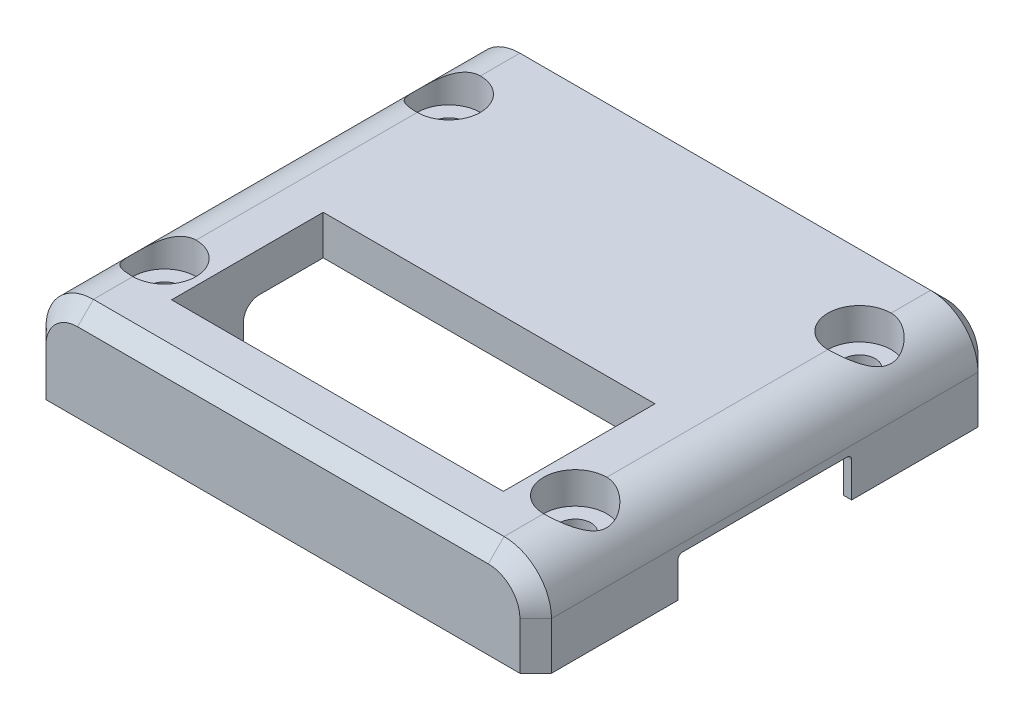
SolidWorks part; units mm, degrees
ref_plane "Front Plane" through (0, 0, 0) normal (0, 0, 1) x (1, 0, 0)
ref_plane "Top Plane" through (0, 0, 0) normal (0, 1, 0) x (1, 0, 0)
ref_plane "Right Plane" through (0, 0, 0) normal (1, 0, 0) x (0, 0, -1)
sketch "Sketch1" plane through (0, 0, 0) normal (0, 1, 0) x (1, 0, 0)
  line L0 (-16, -14.5) -> (16, -14.5)
  line L1 (-16, -14.5) -> (-16, 14.5)
  line L2 (16, -14.5) -> (16, 14.5)
  line L3 (-16, 14.5) -> (16, 14.5)
  line L4 (-16, -14.5) -> (16, 14.5) construction
  line L5 (16, -14.5) -> (-16, 14.5) construction
  point P1 (0, 0)
  dimension "D1" = 32
  dimension "D2" = 29
extrude "Boss-Extrude1" add sketch "Sketch1" along normal blind 6 contours L3 L2 L0 L1
sketch "Sketch2" plane through (0, 6, 0) normal (0, 1, 0) x (1, 0, 0)
  line L0 (-13, -9) -> (13, -9) construction
  line L1 (-13, -9) -> (-13, 9) construction
  line L2 (13, -9) -> (13, 9) construction
  line L3 (-13, 9) -> (13, 9) construction
  line L4 (-13, -9) -> (13, 9) construction
  line L5 (13, -9) -> (-13, 9) construction
  circle A0 centre (-13, 9) radius 1
  circle A1 centre (13, 9) radius 1
  circle A2 centre (13, -9) radius 1
  circle A3 centre (-13, -9) radius 1
  point P1 (0, 0)
  dimension "D1" = 2
  dimension "D2" = 26
  dimension "D3" = 18
extrude "Cut-Extrude1" cut sketch "Sketch2" against normal blind 10
sketch "Sketch3" plane through (0, 6, 0) normal (0, 1, 0) x (1, 0, 0)
  line L0 (0, -6.25) -> (0, 6.25) construction
  line L1 (-10.5, 1.45) -> (10.5, 1.45) construction
  line L2 (-10.5, 1.45) -> (-10.5, 11.05) construction
  line L3 (10.5, 1.45) -> (10.5, 11.05) construction
  line L4 (-10.5, 11.05) -> (10.5, 11.05) construction
  line L5 (-10.5, 1.45) -> (10.5, 11.05) construction
  line L6 (10.5, 1.45) -> (-10.5, 11.05) construction
  line L7 (-10.5, -11.05) -> (10.5, -11.05)
  line L8 (-10.5, -11.05) -> (-10.5, -1.45)
  line L9 (10.5, -11.05) -> (10.5, -1.45)
  line L10 (-10.5, -1.45) -> (10.5, -1.45)
  line L11 (-10.5, -11.05) -> (10.5, -1.45) construction
  line L12 (10.5, -11.05) -> (-10.5, -1.45) construction
  point P4 (0, 0)
  dimension "D1" = 9.6
  dimension "D2" = 21
  dimension "D3" = 12.5
extrude "Cut-Extrude2" cut sketch "Sketch3" against normal blind 10
sketch "Sketch4" plane through (0, 0, 0) normal (0, -1, 0) x (1, 0, 0)
  line L0 (15.5, 13.5) -> (-15.5, 13.5)
  line L1 (15.5, 13.5) -> (15.5, -13.5)
  line L2 (-15.5, 13.5) -> (-15.5, -13.5)
  line L3 (15.5, -13.5) -> (-15.5, -13.5)
  line L4 (15.5, 13.5) -> (-15.5, -13.5) construction
  line L5 (-15.5, 13.5) -> (15.5, -13.5) construction
  line L6 (-16, -14.5) -> (16, -14.5) construction
  point P1 (0, 0)
  dimension "D1" = 31
  dimension "D2" = 1
extrude "Cut-Extrude3" cut sketch "Sketch4" against normal blind 1
fillet "Fillet2" radius 3 2 edges at (-16, 6, 0) (16, 6, 0)
sketch "Sketch5" plane through (0, 6, 0) normal (0, 1, 0) x (1, 0, 0)
  circle A0 centre (-13, 9) radius 2
  circle A1 centre (13, 9) radius 2
  circle A2 centre (13, -9) radius 2
  circle A3 centre (-13, -9) radius 2
  dimension "D1" = 4
extrude "Cut-Extrude4" cut sketch "Sketch5" against normal blind 2
chamfer "Chamfer2" distance 1 angle 45 10 edges at (-16, 1.5, 14.5) (-15.1213, 5.1213, 14.5) (0, 6, 14.5) (15.1213, 5.1213, 14.5) (16, 1.5, 14.5) (-16, 1.5, -14.5) (-15.1213, 5.1213, -14.5) (0, 6, -14.5) (15.1213, 5.1213, -14.5) (16, 1.5, -14.5)
sketch "Sketch6" plane through (0, 0, 0) normal (0, -1, 0) x (1, 0, 0)
  line L0 (-15.5, 13.5) -> (-15.5, -13.5) construction
  line L1 (-15, -5.5) -> (-16, -5.5)
  line L2 (-15, -5.5) -> (-15, 5.5)
  line L3 (-15, 5.5) -> (-16, 5.5)
  line L4 (-16, -5.5) -> (-16, 5.5)
  line L5 (-15, -5.5) -> (-16, 5.5) construction
  line L6 (-15, 5.5) -> (-16, -5.5) construction
  line L7 (-16, 13.5) -> (-16, -13.5) construction
  line L8 (15.5, -13.5) -> (15.5, 13.5) construction
  line L9 (15, -5.5) -> (16, -5.5)
  line L10 (15, -5.5) -> (15, 5.5)
  line L11 (15, 5.5) -> (16, 5.5)
  line L12 (16, -5.5) -> (16, 5.5)
  line L13 (15, -5.5) -> (16, 5.5) construction
  line L14 (15, 5.5) -> (16, -5.5) construction
  line L15 (16, 13.5) -> (16, -13.5) construction
  point P0 (-15.5, 0)
  point P9 (15.5, 0)
  dimension "D1" = 11
extrude "Cut-Extrude5" cut sketch "Sketch6" against normal blind 2.5
fillet "Fillet3" radius 0.3 4 edges at (15.5, 2.5, 5.5) (15.5, 2.5, -5.5) (-15.5, 2.5, -5.5) (-15.5, 2.5, 5.5)
sketch "Sketch7" plane through (0, 1, 0) normal (0, -1, 0) x (1, 0, 0)
  line L0 (-15.5, 13.5) -> (-15.5, 5.5) construction
  line L1 (15.5, -6.5) -> (-15.5, -6.5)
  line L2 (15.5, -6.5) -> (15.5, 6.5)
  line L3 (15.5, 6.5) -> (-15.5, 6.5)
  line L4 (-15.5, -6.5) -> (-15.5, 6.5)
  line L5 (15.5, -6.5) -> (-15.5, 6.5) construction
  line L6 (15.5, 6.5) -> (-15.5, -6.5) construction
  point P0 (0, 0)
  dimension "D1" = 13
extrude "Cut-Extrude6" cut sketch "Sketch7" against normal blind 2.5
fillet "Fillet4" radius 1 3 edges at (0, 3.5, -6.5) (13, 3.5, 6.5) (-13, 3.5, 6.5)
sketch "Эскиз1" plane through (0, 1, 0) normal (0, -1, 0) x (1, 0, 0)
  line L0 (-10.5, 1.45) -> (-10.5, 5.5) construction
  line L1 (-10.5, -1.45) -> (10.5, -1.45)
  line L2 (-10.5, -1.45) -> (-10.5, -13.5)
  line L3 (-10.5, -13.5) -> (10.5, -13.5)
  line L4 (10.5, -1.45) -> (10.5, -13.5)
  line L5 (-10.5, -1.45) -> (10.5, -13.5) construction
  line L6 (-10.5, -13.5) -> (10.5, -1.45) construction
  line L7 (10.5, 5.5) -> (10.5, 1.45) construction
  line L8 (-15.5, -13.5) -> (15.5, -13.5) construction
  line L9 (0, 0) -> (5.1222, 0) construction
  line L10 (10.5, 1.45) -> (-10.5, 1.45) construction
  point P0 (0, -7.475)
extrude "Вырез-Вытянуть1" cut sketch "Эскиз1" against normal up to surface (2.5 mm away) up to face at (0, 3.5, 1.7375)
fillet "Скругление1" radius 1 2 edges at (10.5, 3.5, -9.5) (-10.5, 3.5, -9.5)
sketch "Эскиз2" plane through (0, 0, -13.5) normal (0, 0, 1) x (1, 0, 0)
  line L0 (-15, 0) -> (15, 0) construction
  line L1 (-5.5, 2.5) -> (5.5, 2.5)
  line L2 (-5.5, 2.5) -> (-5.5, 0)
  line L3 (-5.5, 0) -> (5.5, 0)
  line L4 (5.5, 2.5) -> (5.5, 0)
  line L5 (-5.5, 2.5) -> (5.5, 0) construction
  line L6 (-5.5, 0) -> (5.5, 2.5) construction
  line L7 (0, 0) -> (0, 5) construction
  line L8 (13, 5) -> (-13, 5) construction
  point P0 (0, 1.25)
  dimension "D1" = 11
  dimension "D2" = 2.5
extrude "Вырез-Вытянуть2" cut sketch "Эскиз2" against normal through all
fillet "Скругление2" radius 0.3 2 edges at (-5.5, 2.5, -14) (5.5, 2.5, -14)
equation "\"motor_diameter\"= 30"
equation "\"mm_diameter\"= IIF ( \"motor_diameter\" < 34 , 41 , \"motor_diameter\" + 8 )"
equation "\"upper_shafts_diameter\"= 5"
equation "\"upper_shats_length\"= 180"
equation "\"upper_bearing_d1\"= 10"
equation "\"upper_bearing_d2\"= 5"
equation "\"upper_bearing_h\"= 15"
equation "\"lower_shafts_diameter\"= 5"
equation "\"lower_shafts_length\"= 180"
equation "\"lower_bearing_d1\"= 10"
equation "\"lower_bearing_d2\"= 5"
equation "\"lower_bearing_h\"= 15"
equation "\"print_offset\"= 0.5"
equation "\"bh_screws_d\"= 2"
equation "\"bh_screws_h\"= 20"
equation "\"bh_screws_hh_d\"= 3.4"
equation "\"bh_screws_hh_h\"= 2"
equation "\"bh_nut_d\"= 3.8"
equation "\"bh_nut_h\"= 2"
equation "\"motor_screws_d\"= 3"
equation "\"motor_screws_h\"= 16"
equation "\"motor_screws_hh_d\"= 5.5"
equation "\"motor_screws_hh_h\"= 3"
equation "\"plate_hole_distance\"= 25.4"
equation "\"plate_screws_d\"= 6.5"
equation "\"shafts_diameter\"= IIF ( \"mm_diameter\" < 42 , 42 + 8 , \"mm_diameter\" + 8 )"
equation "\"central_hole_diameter\"= 8"
equation "\"bh_thikness\"= 4"
equation "\"D2@Sketch1\"=\"upper_bearing_h\"+\"bh_thikness\"*2+3*2"
